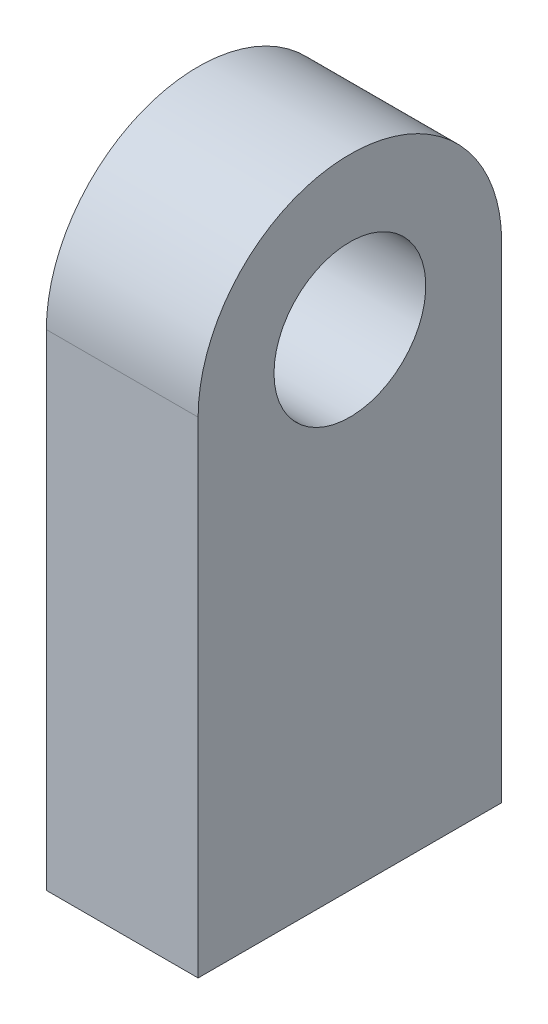
SolidWorks part; units mm, degrees
ref_plane "Front Plane" through (0, 0, 0) normal (0, 0, 1) x (1, 0, 0)
ref_plane "Top Plane" through (0, 0, 0) normal (0, 1, 0) x (1, 0, 0)
ref_plane "Right Plane" through (0, 0, 0) normal (1, 0, 0) x (0, 0, -1)
sketch "Sketch1" plane through (0, 0, 0) normal (1, 0, 0) x (0, 0, -1)
  line L0 (10, 0) -> (-10, 0)
  line L1 (-10, 32) -> (-10, 0)
  line L2 (0, 42) -> (0, 0) construction
  line L3 (10, 32) -> (10, 0)
  arc A0 (-10, 32) -> (10, 32) centre (0, 32) cw
  dimension "D1" = 10
extrude "Boss-Extrude1" add sketch "Sketch1" along normal blind 10 contours A0 L3 L0 L1
sketch "Sketch3" plane through (0, 0, 0) normal (-1, 0, 0) x (0, 0, 1)
  line L0 (-10, 32) -> (10, 32) construction
  line L1 (0, 32) -> (0, 0) construction
hole_wizard "Ø10.0mm Dowel Hole1" positions "3DSketch2" profile "Sketch4" hole size "Ø10.0" standard "ISO"
sketch3d "3DSketch2"
  point P0 (0, 32, 0)
sketch "Sketch4" plane through (0, 32, 0) normal (0, 1, 0) x (0, 0, 1)
  line L0 (0, 0) -> (0, 28.0043)
  line L1 (0, 28.0043) -> (5, 25)
  line L2 (5, 25) -> (5, 0)
  line L5 (5, 0) -> (0, 0)
  line L10 (0, 28.0043) -> (-5, 25) construction
  line L11 (0, -6.35) -> (0, 107.95) construction
  dimension "Hole Dia." = 10
  dimension "Hole Depth" = 25
  dimension "Drill Angle" = 118
